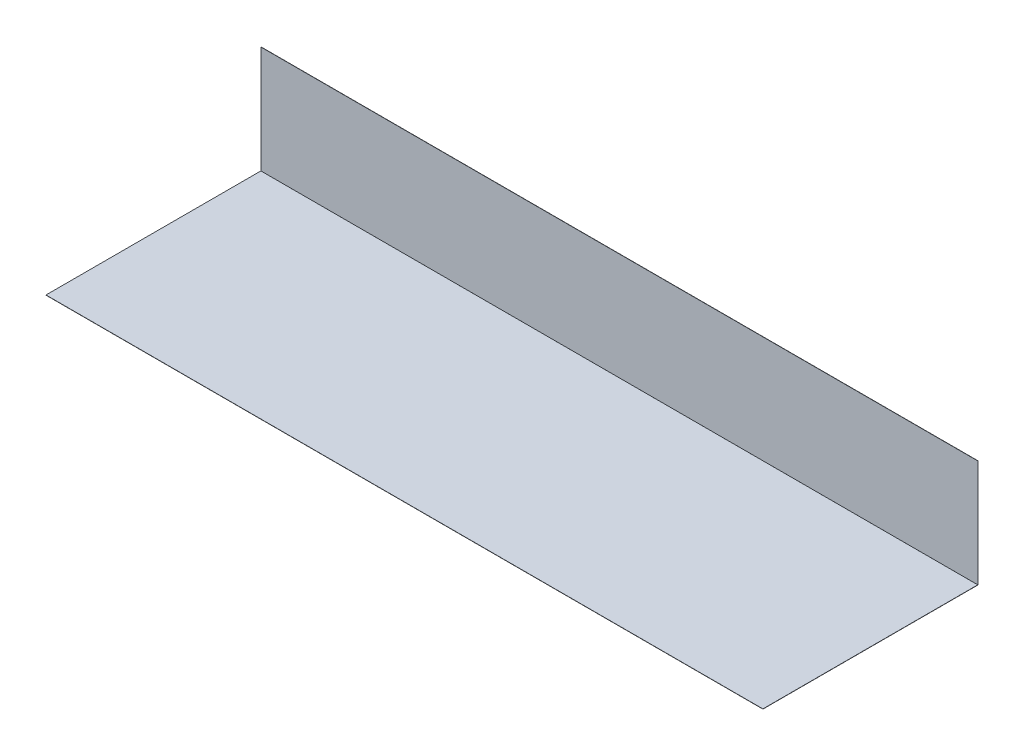
SolidWorks part; units mm, degrees
note: The reader was unsure of these and kept them because the rebuilt part matched: flange length of "边线-法兰1".
ref_plane "前视基准面" through (0, 0, 0) normal (0, 0, 1) x (1, 0, 0)
ref_plane "上视基准面" through (0, 0, 0) normal (0, 1, 0) x (1, 0, 0)
ref_plane "右视基准面" through (0, 0, 0) normal (1, 0, 0) x (0, 0, -1)
sketch "草图1" plane through (0, 0, 0) normal (0, 0, 1) x (1, 0, 0)
  line L1 (0, 0) -> (-10000, 0)
  dimension "D1" = 10000
base flange "基体-法兰1" sketch "草图1" end condition mid plane depth 3000 reverse direction no thickness 3 reverse thickness direction no bend radius 0.1
edge flange "边线-法兰1" sketch "草图8" flange angle 90 flange length 1500 flange position material inside bend radius 0.1 thickness 3 relief rectangular parameters "D6"=10
sketch "草图8" plane through (0, 3, -1500) normal (0, 0, -1) x (-1, 0, 0)
  line L0 (0, 0) -> (10000, 0) construction
  line L1 (0, 0) -> (10000, 0)
  line L2 (0, 0) -> (0, 1497)
  line L3 (0, 1497) -> (10000, 1497)
  line L4 (10000, 1497) -> (10000, 0)
bend "边线折弯1" bend radius 0.1 bend angle 90 parameters "D5"=1
sketch "草图9" plane through (0, 0, 0) normal (0, -1, 0) x (1, 0, 0)
  circle A0 centre (-5580.1049, -302.8763) radius 124.5856
  point P2 (-5580.1049, -302.8763)
extrude "凸台-拉伸1" add sketch "草图9" along normal blind 100
sketch "折弯-线1" plane through (0, 0, 0) normal (0, 1, 0) x (1, 0, 0)
sketch "边界框1" plane through (0, 0, 0) normal (0, 1, 0) x (1, 0, 0)
sheet metal parameters "钣金6" thickness 3 parameters "D1"=0.1
flat pattern "平板型式6" [suppressed]
sketch "折弯-线2" plane through (0, 0, 0) normal (0, 1, 0) x (1, 0, 0)
sketch "边界框2" [suppressed] plane through (0, 0, 0) normal (0, 1, 0) x (1, 0, 0)
sheet metal parameters "钣金7" thickness 3 parameters "D1"=0.1
flat pattern "平板型式6" [suppressed]
sketch "折弯-线2" plane through (0, 0, 0) normal (0, 1, 0) x (1, 0, 0)
sketch "边界框2" [suppressed] plane through (0, 0, 0) normal (0, 1, 0) x (1, 0, 0)
bend of the flat pattern "展平-<边线折弯1>1"
sheet metal parameters "钣金9" thickness 3 parameters "D1"=0.1
flat pattern "平板型式6" [suppressed]
sketch "折弯-线2" plane through (0, 0, 0) normal (0, 1, 0) x (1, 0, 0)
sketch "边界框2" [suppressed] plane through (0, 0, 0) normal (0, 1, 0) x (1, 0, 0)
bend of the flat pattern "展平-<边线折弯1>1"
